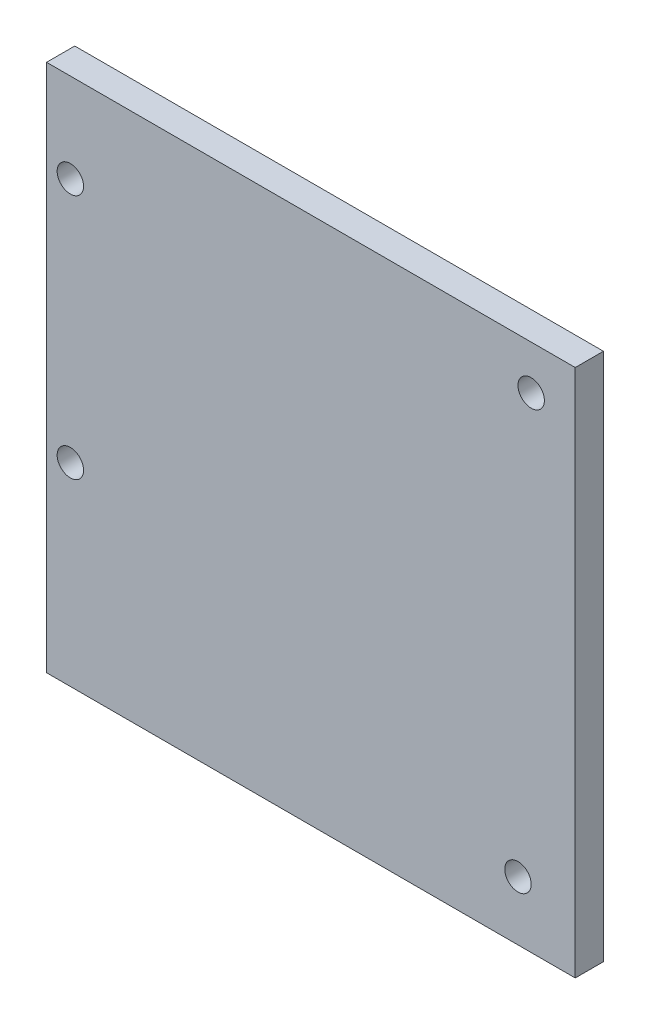
SolidWorks part; units mm, degrees
ref_plane "Front Plane" through (0, 0, 0) normal (0, 0, 1) x (1, 0, 0)
ref_plane "Top Plane" through (0, 0, 0) normal (0, 1, 0) x (1, 0, 0)
ref_plane "Right Plane" through (0, 0, 0) normal (1, 0, 0) x (0, 0, -1)
sketch "Sketch2" plane through (0, 0, 0) normal (0, 0, 1) x (1, 0, 0)
  line L1 (-32.5494, -8.3608) -> (27.4506, -8.3608)
  line L2 (-32.5494, -8.3608) -> (-32.5494, 51.6392)
  line L3 (-32.5494, 51.6392) -> (27.4506, 51.6392)
  line L4 (27.4506, -8.3608) -> (27.4506, 51.6392)
  dimension "D1" = 60
  dimension "D2" = 60
extrude "Boss-Extrude2" add sketch "Sketch2" along normal blind 3.2
sketch "Sketch3" plane through (0, 0, 3.2) normal (0, 0, 1) x (1, 0, 0)
  line L0 (22.4506, 46.6392) -> (22.4506, 1.9043) construction
  line L4 (27.4506, 51.6392) -> (-32.5494, 51.6392) construction
  line L6 (27.4506, -8.3608) -> (27.4506, 51.6392) construction
  circle A0 centre (20.9506, -1.6608) radius 1.5
  circle A1 centre (22.4506, 46.6392) radius 1.5
  circle A2 centre (-29.8494, 13.6392) radius 1.5
  circle A3 centre (-29.8494, 41.5392) radius 1.5
  dimension "D1" = 3
  dimension "D2" = 48.3
  dimension "D7" = 5
  dimension "D3" = 27.9
  dimension "D4" = 5.1
  dimension "D5" = 50.8
  dimension "D6" = 5
extrude "Cut-Extrude1" cut sketch "Sketch3" against normal blind 3.2
